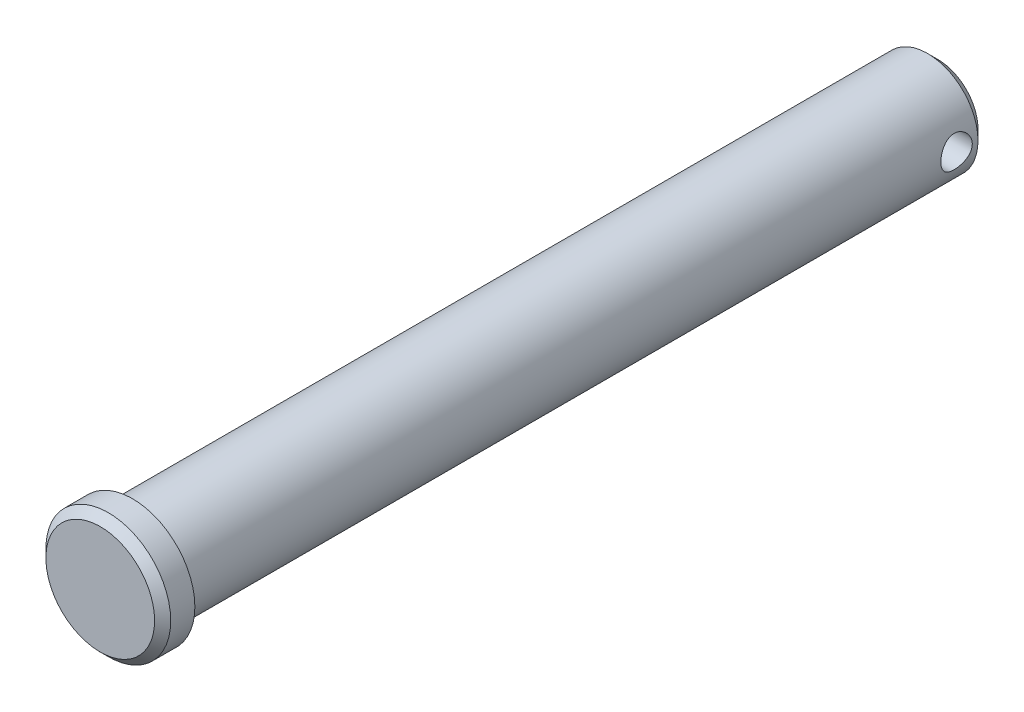
SolidWorks part; units mm, degrees
ref_plane "Front Plane" through (0, 0, 0) normal (0, 0, 1) x (1, 0, 0)
ref_plane "Top Plane" through (0, 0, 0) normal (0, 1, 0) x (1, 0, 0)
ref_plane "Right Plane" through (0, 0, 0) normal (1, 0, 0) x (0, 0, -1)
sketch "Sketch1" plane through (0, 0, 0) normal (1, 0, 0) x (0, 0, -1)
  line L0 (-52.832, 0) -> (52.832, 0) construction
  line L1 (52.832, 6.35) -> (52.832, -6.35) construction
  line L2 (-48.768, 7.874) -> (-48.768, -7.874) construction
  line L3 (-52.832, 7.874) -> (-52.832, -7.874) construction
  circle A0 centre (48.8601, 0) radius 1.9812
  point P11 (-48.768, 0)
  dimension "Through Hole Dia." = 3.9624
  dimension "Usable Length" = 95.6469
  dimension "Length" = 101.6
  dimension "Diameter" = 12.7
  dimension "Head Dia" = 15.748
  dimension "Head Height" = 4.064
sketch "Sketch2" plane through (0, 0, 0) normal (1, 0, 0) x (0, 0, -1)
  line L0 (51.562, 6.35) -> (-48.768, 6.35)
  line L1 (-48.768, 7.874) -> (-48.768, -7.874) construction
  line L2 (-48.768, 6.35) -> (-48.768, 7.874)
  line L3 (-48.768, 7.874) -> (-51.816, 7.874)
  line L4 (-52.832, 6.858) -> (-52.832, 0)
  line L5 (-52.832, 0) -> (52.832, 0)
  line L6 (52.832, 0) -> (52.832, 5.08)
  line L11 (51.562, 6.35) -> (52.832, 5.08)
  line L12 (-51.816, 7.874) -> (-52.832, 6.858)
  dimension "D1" = 45
  dimension "D2" = 1.27
  dimension "D3" = 1.016
revolve "Revolve1" add sketch "Sketch2" angle 360 about L5
sketch "Sketch3" plane through (0, 0, 0) normal (1, 0, 0) x (0, 0, -1)
  circle A0 centre (48.8601, 0) radius 1.9812 construction
  circle A1 centre (48.8601, 0) radius 1.9812
extrude "Cut-Extrude1" cut sketch "Sketch3" against normal through all both and the other way through all
ref_axis "Center Axis 1" through (-6.35, 0, -48.8601) along (1, 0, 0)
ref_plane "Contact Plane 1" through (0, 0, 48.768) normal (0, 0, -1) x (-1, 0, 0)
equation "\"D2@Sketch2\"=\"Diameter@Sketch1\"/10"
equation "\"D3@Sketch2\"=\"Head Height@Sketch1\"/4"
